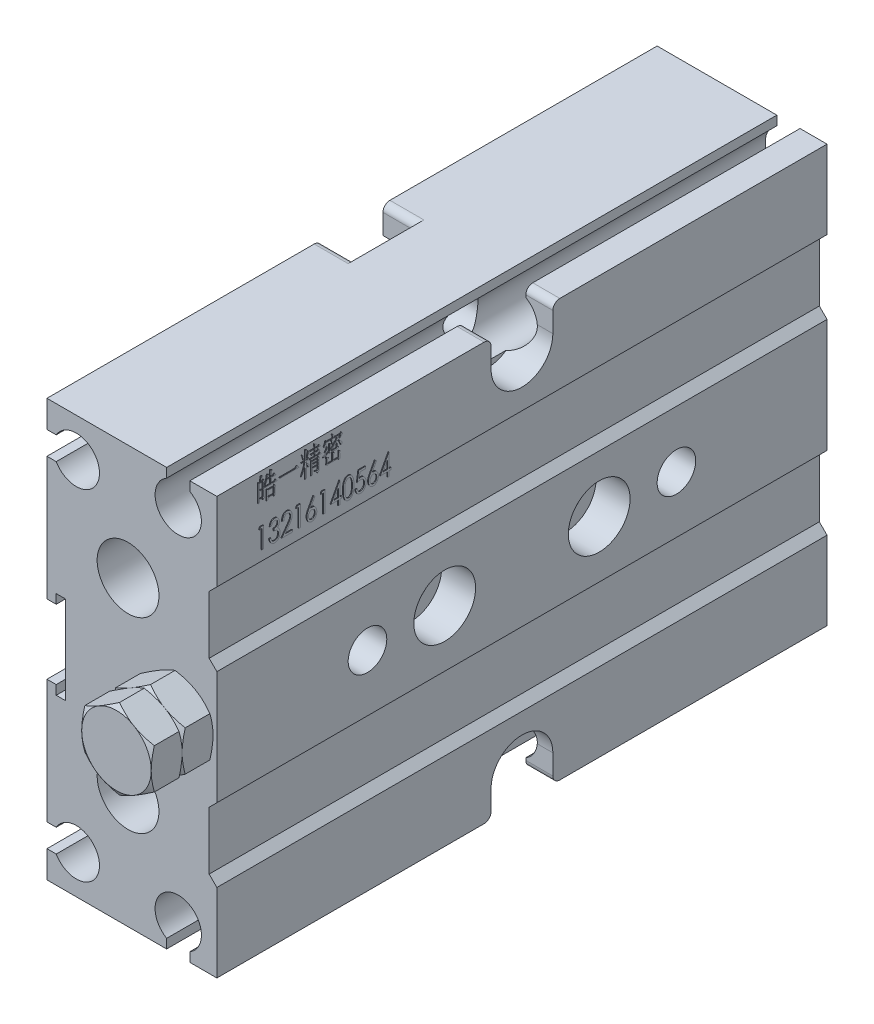
SolidWorks part; units mm, degrees
ref_plane "前视基准面" through (0, 0, 0) normal (0, 0, 1) x (1, 0, 0)
ref_plane "上视基准面" through (0, 0, 0) normal (0, 1, 0) x (1, 0, 0)
ref_plane "右视基准面" through (0, 0, 0) normal (1, 0, 0) x (0, 0, -1)
sketch "草图1" plane through (0, 0, 0) normal (1, 0, 0) x (0, 0, -1)
  line L0 (0, 0) -> (121, 0) construction
  line L1 (121, 0) -> (121, 27)
  line L2 (121, 27) -> (42, 27)
  line L3 (42, 27) -> (42, 0)
  line L4 (42, 12.1) -> (8, 12.1) construction
  line L5 (101.5, 0) -> (101.5, 6) construction
  line L6 (8, 16.1) -> (42, 16.1)
  line L7 (8, 8.1) -> (42, 8.1)
  line L8 (0, 0) -> (0, 26.5)
  line L9 (0, 26.5) -> (8, 26.5)
  line L10 (8, 26.5) -> (8, 0)
  line L11 (4, 26.5) -> (4, 0) construction
  line L12 (4, 17) -> (-1, 17) construction
  line L13 (8, 2.55) -> (9, 2.55)
  line L14 (9, 2.55) -> (9, 0)
  line L15 (0, 7.6) -> (5.5, 7.6)
  line L16 (5.5, 7.6) -> (5.5, 9.35)
  line L17 (5.5, 9.35) -> (8, 9.35)
  line L18 (71.5, 4) -> (71.5, 8.4) construction
  line L19 (81.5, 27) -> (81.5, 0) construction
  line L20 (85.5, 23.5) -> (89.9, 23.5) construction
  circle A2 centre (4, 17) radius 2
  circle A3 centre (71.5, 0) radius 4
  circle A4 centre (71.5, 0) radius 2.25
  circle A5 centre (91.5, 0) radius 4
  circle A6 centre (91.5, 0) radius 2.25
  circle A7 centre (101.5, 0) radius 2.5
  circle A8 centre (61.5, 0) radius 2.5
  circle A9 centre (81.5, 23.5) radius 4
  circle A10 centre (81.5, 23.5) radius 2.25
  point P8 (67, 0)
  point P28 (8, 15.2)
  point P44 (34, 0)
  dimension "D5" = 8
  dimension "D12" = 4
  dimension "D22" = 8
  dimension "D24" = 4.5
  dimension "D3" = 5
  dimension "D25" = 8
  dimension "D27" = 4.5
  dimension "D1" = 54
  dimension "XC" = 25
  dimension "B" = 29.5
  dimension "D4" = 54
  dimension "D6" = 6
  dimension "D7" = 24.2
  dimension "D8" = 8
  dimension "D9" = 53
  dimension "D10" = 8
  dimension "D11" = 34
  dimension "D13" = 5
  dimension "D14" = 5.1
  dimension "D15" = 1
  dimension "D16" = 6.2
  dimension "D17" = 25
  dimension "D18" = 9
  dimension "D19" = 5.5
  dimension "D20" = 5.5
  dimension "D21" = 47
  dimension "D23" = 4.4
  dimension "P" = 40
  dimension "D26" = 4.4
  dimension "E" = 39.5
  dimension "A" = 20
sketch "草图2" plane through (0, 0, 0) normal (0, 0, 1) x (1, 0, 0)
  line L0 (-10.5, 0) -> (11.5, 0) construction
  line L1 (-10.5, 27) -> (11.5, 27)
  line L2 (-10.5, 27) -> (-10.5, -27)
  line L3 (-10.5, -27) -> (11.5, -27)
  line L4 (11.5, 27) -> (11.5, -27)
  line L5 (0, 27) -> (0, -27) construction
  line L7 (-10, 26.5) -> (10, 26.5)
  line L8 (-10, 26.5) -> (-10, -26.5)
  line L9 (-10, -26.5) -> (10, -26.5)
  line L10 (10, 26.5) -> (10, -26.5)
  circle A0 centre (0, 23.5) radius 2
  point P17 (6.5, 0)
  dimension "D3" = 4
  dimension "D1" = 11.5
  dimension "D2" = 20
  dimension "D4" = 47
  dimension "D5" = 22
  dimension "D6" = 6.5
sketch "草图3" plane through (0, 0, 0) normal (0, 1, 0) x (1, 0, 0)
  line L0 (0, 0) -> (0, 121) construction
  line L1 (0, 0) -> (0, 121) construction
  line L2 (0, 9) -> (0, 34)
  line L3 (-10.5, 0) -> (11.5, 0) construction
  line L4 (-10.5, 0) -> (11.5, 0)
  line L5 (-10.5, 0) -> (-10.5, 8)
  line L6 (-10.5, 8) -> (-3.1, 8)
  line L7 (11.5, 0) -> (11.5, 8)
  line L8 (-3.1, 8) -> (-3.1, 7)
  line L9 (3.1, 8) -> (3.1, 7)
  line L10 (-3.1, 7) -> (3.1, 7)
  line L11 (3.1, 8) -> (11.5, 8)
  circle A0 centre (0, 105.5) radius 2.5
  circle A1 centre (0, 57.5) radius 2.5
  point P6 (0, 10)
  dimension "D1" = 5
  dimension "D3" = 15.5
  dimension "D2" = 15.5
  dimension "D4" = 1
  dimension "D5" = 6.2
  dimension "D6" = 3
sketch "草图4" plane through (0, 0, 0) normal (0, 0, 1) x (1, 0, 0)
  line L0 (-10.5, 23.5) -> (-10.5, 20.5) construction
  line L1 (11.5, 27) -> (11.5, -27) construction
  line L2 (-10.5, -27) -> (11.5, -27) construction
  line L3 (-10.5, 27) -> (-10.5, -27) construction
  line L4 (-5, 27) -> (-10.5, 27)
  line L5 (11.5, 27) -> (11.5, 16.85)
  line L6 (-10.5, -27) -> (5, -27)
  line L7 (-10.5, 27) -> (-10.5, 23.5)
  line L8 (0, 27) -> (0, -27) construction
  line L9 (0, 27) -> (0, -27) construction
  line L10 (5, 25.8) -> (5, 27)
  line L11 (8, 25.8) -> (8, 27)
  line L12 (-10.5, 23.5) -> (-9.3, 23.5)
  line L13 (-10.5, 20.5) -> (-9.3, 20.5)
  line L14 (-10.5, 0) -> (11.5, 0) construction
  line L15 (-10.5, 0) -> (11.5, 0) construction
  line L16 (11.5, 16.85) -> (10.5, 15.85)
  line L17 (10.5, 15.85) -> (10.5, 8.35)
  line L18 (10.5, 8.35) -> (11.5, 7.35)
  line L19 (11.5, 7.35) -> (11.5, -7.35)
  line L20 (11.5, -16.85) -> (10.5, -15.85)
  line L21 (10.5, -15.85) -> (10.5, -8.35)
  line L22 (10.5, -8.35) -> (11.5, -7.35)
  line L23 (11.5, -16.85) -> (11.5, -27)
  line L24 (-5, 27) -> (5, 27)
  line L25 (8, 27) -> (11.5, 27)
  line L26 (-10.5, 4.5) -> (-9.3, 4.5)
  line L27 (-9.3, 4.5) -> (-9.3, 5.7)
  line L28 (-9.3, 5.7) -> (-8.1, 5.7)
  line L29 (-8.1, 5.7) -> (-8.1, -5.7)
  line L30 (-9.3, -5.7) -> (-8.1, -5.7)
  line L31 (-9.3, -4.5) -> (-9.3, -5.7)
  line L32 (-10.5, -4.5) -> (-9.3, -4.5)
  line L33 (-10.5, -4.5) -> (-10.5, -20.5)
  line L34 (-10.5, 20.5) -> (-10.5, 4.5)
  line L35 (5, 27) -> (8, 27) construction
  line L36 (-10.5, -20.5) -> (-9.3, -20.5)
  line L37 (-10.5, -23.5) -> (-9.3, -23.5)
  line L38 (-10.5, -23.5) -> (-10.5, -27)
  line L39 (5, -25.8) -> (5, -27)
  line L40 (8, -25.8) -> (8, -27)
  line L41 (8, -27) -> (11.5, -27)
  arc A0 (5, 25.8) -> (8, 25.8) centre (6.5, 23.2019) ccw
  arc A1 (-9.3, 20.5) -> (-9.3, 23.5) centre (-6.7019, 22) ccw
  arc A2 (-9.3, -20.5) -> (-9.3, -23.5) centre (-6.7019, -22) cw
  arc A3 (5, -25.8) -> (8, -25.8) centre (6.5, -23.2019) cw
  point P32 (-8.1, 0)
  point P35 (10.5, 12.1)
  dimension "D1" = 3
  dimension "D2" = 3
  dimension "D3" = 1.2
  dimension "D4" = 3.5
  dimension "D5" = 1
  dimension "D7" = 9.5
  dimension "D8" = 1.2
  dimension "D9" = 9
extrude "凸台-拉伸1" add sketch "草图4" against normal up to vertex (121 mm away) from vertex at -42 starting at point (0, 27, -42)
sketch "草图5" plane through (11.5, 0, 0) normal (1, 0, 0) x (0, 0, -1)
  circle A2 centre (61.5, 0) radius 2.5
  circle A3 centre (101.5, 0) radius 2.5
  circle A4 centre (61.5, 0) radius 2.5 construction
  circle A5 centre (101.5, 0) radius 2.5 construction
extrude "P" cut sketch "草图5" against normal blind 6
cosmetic thread "装饰螺纹线1" parameters "D2"=5.1
cosmetic thread "装饰螺纹线2" parameters "D2"=5.1
sketch "草图6" plane through (-10.5, 0, 0) normal (-1, 0, 0) x (0, 0, 1)
  circle A0 centre (-71.5, 0) radius 4 construction
  circle A1 centre (-91.5, 0) radius 4 construction
  circle A2 centre (-71.5, 0) radius 4
  circle A3 centre (-91.5, 0) radius 4
extrude "切除-拉伸2" cut sketch "草图6" against normal blind 4.4
sketch "草图7" plane through (-10.5, 0, 0) normal (-1, 0, 0) x (0, 0, 1)
  circle A0 centre (-91.5, 0) radius 2.25 construction
  circle A1 centre (-71.5, 0) radius 2.25 construction
  circle A2 centre (-91.5, 0) radius 2.25
  circle A3 centre (-71.5, 0) radius 2.25
extrude "切除-拉伸3" cut sketch "草图7" against normal through all
sketch "草图24" plane through (11.5, 0, 0) normal (1, 0, 0) x (0, 0, -1)
  circle A0 centre (71.5, 0) radius 4 construction
  circle A1 centre (71.5, 0) radius 4
  circle A2 centre (91.5, 0) radius 4 construction
  circle A3 centre (91.5, 0) radius 4
extrude "切除-拉伸13" cut sketch "草图24" against normal blind 4.4
sketch "草图8" plane through (0, -27, 0) normal (0, -1, 0) x (1, 0, 0)
  circle A0 centre (0, -57.5) radius 2.5 construction
  circle A1 centre (0, -105.5) radius 2.5 construction
  circle A2 centre (0, -57.5) radius 2.5
  circle A3 centre (0, -105.5) radius 2.5
extrude "切除-拉伸4" cut sketch "草图8" against normal blind 6
cosmetic thread "装饰螺纹线3" parameters "D2"=5.1
cosmetic thread "装饰螺纹线4" parameters "D2"=5.1
sketch "草图9" plane through (0, 0, -121) normal (0, 0, -1) x (-1, 0, 0)
  line L0 (0, 0) -> (0, 27) construction
  line L2 (10.5, 0) -> (-11.5, 0) construction
  line L3 (10.5, 0) -> (-11.5, 0) construction
  circle A0 centre (0, 12.1) radius 8.05
  circle A1 centre (0, -12.1) radius 8.05
  dimension "D1" = 16.1
extrude "切除-拉伸5" cut sketch "草图9" against normal blind 1
sketch "草图10" plane through (0, 0, -42) normal (0, 0, 1) x (1, 0, 0)
  line L0 (-10.5, 0) -> (11.5, 0) construction
  line L1 (-10.5, 0) -> (11.5, 0) construction
  circle A0 centre (0, 12.1) radius 4
  circle A1 centre (0, -12.1) radius 4
extrude "切除-拉伸6" cut sketch "草图10" against normal blind 25
sketch "草图28" plane through (0, 0, -42) normal (0, 0, 1) x (1, 0, 0)
  line L1 (6.5, 5.1962) -> (2, 2.5981)
  line L2 (2, 2.5981) -> (2, -2.5981)
  line L3 (2, -2.5981) -> (6.5, -5.1962)
  line L4 (6.5, -5.1962) -> (11, -2.5981)
  line L5 (11, -2.5981) -> (11, 2.5981)
  line L6 (11, 2.5981) -> (6.5, 5.1962)
  circle A0 centre (6.5, 0) radius 4.5 construction
  dimension "D1" = 9
extrude "凸台-拉伸4" add sketch "草图28" along normal up to vertex (8 mm away) up to point (0, 0, -34)
sketch "草图29" plane through (0, 0, 0) normal (0, 1, 0) x (1, 0, 0)
  line L0 (11, 42) -> (12.7321, 42)
  line L1 (12.7321, 42) -> (12.7321, 41)
  line L2 (12.7321, 41) -> (11, 42)
  line L3 (6.5, 38) -> (6.5, 42) construction
  line L4 (6.5, 34) -> (6.5, 42) construction
  line L5 (3.5, 42) -> (9.5, 42) construction
  line L6 (11, 42) -> (6.5, 42) construction
  line L7 (6.5, 38) -> (6.5, 34) construction
  line L8 (6.5, 40) -> (11, 40) construction
  line L9 (11, 34) -> (11, 42) construction
  line L10 (6.5, 36) -> (11, 36) construction
  line L11 (6.5, 38) -> (11, 38) construction
  line L12 (12.7321, 35) -> (11, 34)
  line L13 (12.7321, 34) -> (12.7321, 35)
  line L14 (11, 34) -> (12.7321, 34)
  line L16 (12.7321, 38) -> (12.7321, 39)
  line L17 (12.7321, 39) -> (11, 38)
  line L18 (11, 38) -> (12.7321, 37)
  line L19 (12.7321, 37) -> (12.7321, 38)
  dimension "D1" = 1
  dimension "D2" = 30
revolve "切除-旋转2" cut sketch "草图29" angle 360 mid plane about L3
sketch "草图31" plane through (11.5, 0, 0) normal (1, 0, 0) x (0, 0, -1)
  circle A0 centre (81.5, 23.5) radius 2.25 construction
  circle A1 centre (81.5, 23.5) radius 2.25
extrude "切除-拉伸14" cut sketch "草图31" against normal through all
sketch "草图32" plane through (11.5, 0, 0) normal (1, 0, 0) x (0, 0, -1)
  line L0 (77.5, 23.5) -> (77.5, 27)
  line L1 (121, 27) -> (42, 27) construction
  line L3 (85.5, 23.5) -> (85.5, 27)
  line L4 (85.5, 27) -> (77.5, 27)
  circle A1 centre (81.5, 23.5) radius 4 construction
  arc A2 (77.5, 23.5) -> (85.5, 23.5) centre (81.5, 23.5) ccw
extrude "切除-拉伸15" cut sketch "草图32" against normal blind 4.4
sketch "草图33" plane through (-10.5, 0, 0) normal (-1, 0, 0) x (0, 0, 1)
  line L0 (-85.5, 23.5) -> (-85.5, 27)
  line L1 (-85.5, 27) -> (-77.5, 27)
  line L2 (-121, 27) -> (-42, 27) construction
  line L3 (-77.5, 27) -> (-77.5, 23.5)
  circle A0 centre (-81.5, 23.5) radius 4 construction
  arc A1 (-85.5, 23.5) -> (-77.5, 23.5) centre (-81.5, 23.5) ccw
extrude "切除-拉伸16" cut sketch "草图33" against normal blind 4.4
mirror "镜向6" about plane through (0, 0, 0) normal (0, 1, 0) of "切除-拉伸16", "切除-拉伸15", "切除-拉伸14"
fillet "圆角1" radius 0.9 8 edges at (-8.3, -27, -77.5) (-8.3, -27, -85.5) (9.75, -27, -77.5) (9.75, -27, -85.5) (9.75, 27, -77.5) (9.75, 27, -85.5) (-8.3, 27, -77.5) (-8.3, 27, -85.5)
sketch "草图11" plane through (0, 0, 0) normal (0, 0, 1) x (1, 0, 0)
  line L0 (-10, -26.5) -> (10, -26.5) construction
  line L1 (10, 26.5) -> (10, -26.5) construction
  line L2 (-10, 26.5) -> (-10, -26.5) construction
  line L3 (-10, 26.5) -> (10, 26.5) construction
  line L4 (-10, -26.5) -> (10, -26.5)
  line L5 (10, 26.5) -> (10, -26.5)
  line L6 (-10, 26.5) -> (-10, -26.5)
  line L7 (-10, 26.5) -> (10, 26.5)
extrude "凸台-拉伸2" add sketch "草图11" against normal up to vertex (8 mm away) separate body up to point (0, 26.5, -8)
sketch "草图12" plane through (0, 26.5, 0) normal (0, 1, 0) x (1, 0, 0)
  line L0 (-3.1, 8) -> (-3.1, 7) construction
  line L1 (-3.1, 7) -> (3.1, 7) construction
  line L2 (3.1, 8) -> (3.1, 7) construction
  line L3 (-3.1, 8) -> (-3.1, 7)
  line L4 (-3.1, 7) -> (3.1, 7)
  line L5 (3.1, 8) -> (3.1, 7)
  line L6 (-3.1, 8) -> (3.1, 8)
extrude "切除-拉伸7" cut sketch "草图12" against normal through all
sketch "草图13" plane through (0, 0, 0) normal (1, 0, 0) x (0, 0, -1)
  line L0 (0, 7.6) -> (5.5, 7.6) construction
  line L1 (5.5, 7.6) -> (5.5, 9.35) construction
  line L2 (5.5, 9.35) -> (8, 9.35) construction
  line L3 (0, 7.6) -> (5.5, 7.6)
  line L4 (5.5, 7.6) -> (5.5, 9.35)
  line L5 (5.5, 9.35) -> (8, 9.35)
  line L6 (42, 12.1) -> (8, 12.1) construction
  line L7 (42, 12.1) -> (8, 12.1) construction
  line L8 (0, 7.6) -> (0, 12.1)
  line L9 (0, 0) -> (0, 26.5) construction
  line L10 (0, 12.1) -> (8, 12.1)
  line L11 (8, 12.1) -> (8, 9.35)
revolve "切除-旋转1" cut sketch "草图13" angle 360 mid plane about L7
sketch "草图18" plane through (0, 0, 0) normal (0, 0, 1) x (1, 0, 0)
  circle A0 centre (0, 23.5) radius 2 construction
  circle A1 centre (0, 23.5) radius 2
extrude "切除-拉伸10" cut sketch "草图18" against normal through all
cosmetic thread "装饰螺纹线5" parameters "D2"=4.1
mirror "镜向1" about plane through (0, 0, 0) normal (0, 1, 0) of "切除-拉伸10", "切除-旋转1"
sketch "草图19" plane through (10, 0, 0) normal (1, 0, 0) x (0, 0, -1)
  circle A0 centre (4, 17) radius 2 construction
  circle A1 centre (4, 17) radius 2
extrude "切除-拉伸11" cut sketch "草图19" against normal blind 5
cosmetic thread "装饰螺纹线6" parameters "D2"=4.1
mirror "镜向2" about plane through (0, 0, 0) normal (0, 1, 0) of "切除-拉伸11"
mirror "镜向3" about plane through (0, 0, 0) normal (1, 0, 0) of "镜向2", "切除-拉伸11"
sketch "螺钉草图1" plane through (-2.0166, 5.7609, -5.5) normal (0, 0, 1) x (1, 0, 0)
  circle A0 centre (2.0166, 6.3391) radius 4.05
  dimension "D1" = 8.1
extrude "拉伸-螺钉(内六角)" add sketch "螺钉草图1" along normal blind 4.86
fillet "圆角-螺钉(内六角)" radius 0.27 1 edges at (4.05, 12.1, -0.64)
sketch "螺钉草图2" plane through (0, 6.5, -0.64) normal (0, 0, 1) x (1, 0, 0)
  line L1 (2.8059, 5.6) -> (1.403, 8.03)
  line L2 (1.403, 8.03) -> (-1.403, 8.03)
  line L3 (-1.403, 8.03) -> (-2.8059, 5.6)
  line L4 (-2.8059, 5.6) -> (-1.403, 3.17)
  line L5 (-1.403, 3.17) -> (1.403, 3.17)
  line L6 (1.403, 3.17) -> (2.8059, 5.6)
  circle A0 centre (0, 5.6) radius 2.43 construction
  dimension "D1" = 4.86
extrude "切除-螺钉(内六角)" cut sketch "螺钉草图2" against normal blind 2.835
other "螺钉头<1>"
mirror "镜向5" about plane through (0, 0, 0) normal (0, 1, 0) of "拉伸-螺钉(内六角)", "圆角-螺钉(内六角)", "切除-螺钉(内六角)"
sketch "草图30" plane through (0, 0, -8) normal (0, 0, -1) x (-1, 0, 0)
  line L1 (-3.1, -26.5) -> (-3.1, 26.5) construction
  circle A0 centre (-6.5, 0) radius 2.4
  point P3 (-4.1, 0)
  dimension "D1" = 1
extrude "凸台-拉伸5" add sketch "草图30" along normal up to vertex (1 mm away) up to point (0, 2.55, -9)
sketch "草图20" plane through (0, 0, 0) normal (1, 0, 0) x (0, 0, -1)
  line L1 (7, 16.1) -> (42, 16.1)
  line L2 (7, 16.1) -> (7, 12.1)
  line L3 (7, 12.1) -> (42, 12.1)
  line L4 (42, 16.1) -> (42, 12.1)
revolve "旋转1" add sketch "草图20" angle 360 mid plane about L3
sketch "草图21" plane through (0, 0, 0) normal (0, 1, 0) x (1, 0, 0)
  line L1 (3.1, 10) -> (4, 10) construction
  line L2 (3.1, 10) -> (3.1, 7)
  line L3 (3.1, 7) -> (4, 7)
  line L4 (4, 10) -> (4, 7)
  line L5 (4, 7) -> (4, 42) construction
  line L6 (0, 4) -> (0, -1) construction
  line L7 (0, 4) -> (0, -1) construction
  line L8 (-4, 10) -> (-4, 7)
  line L9 (-3.1, 7) -> (-4, 7)
  line L10 (-3.1, 10) -> (-3.1, 7)
  line L11 (-3.1, 10) -> (-4, 10) construction
  line L12 (4, 11) -> (4, 10)
  line L13 (-4, 11) -> (-4, 10)
  arc A0 (3.1, 10) -> (4, 11) centre (4.1056, 10) cw
  arc A1 (-3.1, 10) -> (-4, 11) centre (-4.1056, 10) ccw
  dimension "D1" = 1
extrude "切除-拉伸12" cut sketch "草图21" against normal through all and the other way through all
mirror "镜向4" about plane through (0, 0, 0) normal (0, 1, 0) of bodies 122
combine bodies "组合1" operation type add bodies to combine 131 122 123
delete or keep bodies "实体-删除1" type delete bodies bodies 124
sketch "草图34" plane through (11.5, -81.6981, -88.2654) normal (1, 0, 0) x (0, 0, -1)
  line L0 (-41.2654, 108.6981) -> (-41.2654, 105.3148) construction
  line L1 (-46.2654, 98.5481) -> (-46.2654, 108.6981) construction
  line L2 (-41.2654, 105.3148) -> (-41.2654, 101.9315) construction
  line L3 (-41.2654, 101.9315) -> (-41.2654, 98.5481) construction
  line L4 (-41.2654, 105.3148) -> (-46.2654, 105.3148) construction
  line L5 (32.7346, 98.5481) -> (-46.2654, 98.5481) construction
  line L6 (-11.6654, 108.6981) -> (-46.2654, 108.6981) construction
  line L9 (-41.2654, 105.3148) -> (-36.2654, 105.3148) construction
  line L10 (-36.2654, 105.3148) -> (-31.2654, 105.3148) construction
  line L11 (-31.2654, 105.3148) -> (-26.2654, 105.3148) construction
  line L12 (-26.2654, 105.3148) -> (-21.2654, 105.3148) construction
  line L13 (-21.2654, 105.3148) -> (-16.2654, 105.3148) construction
  text T0 "皓一精密\r\n13216140564" font "Century Gothic" height in points 10
  dimension "D1" = 5
extrude "凸台-拉伸6" add sketch "草图34" along normal blind 0.1
